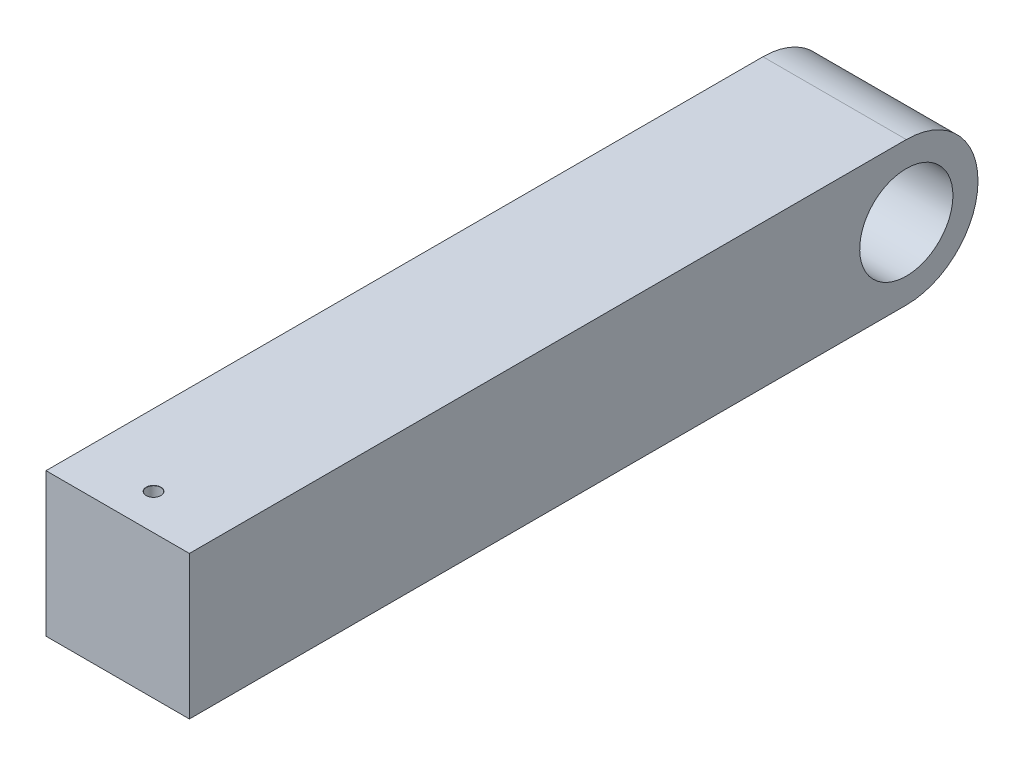
SolidWorks part; units mm, degrees
ref_plane "Front Plane" through (0, 0, 0) normal (1, 0, 0) x (0, 1, 0)
ref_plane "Top Plane" through (0, 0, 0) normal (0, 0, 1) x (0, 1, 0)
ref_plane "Right Plane" through (0, 0, 0) normal (0, 1, 0) x (-1, 0, 0)
sketch "Sketch1" plane through (0, 0, 0) normal (0, 0, 1) x (0, 1, 0)
  line L1 (-10, 10) -> (10, 10)
  line L2 (-10, 10) -> (-10, -10)
  line L3 (-10, -10) -> (10, -10)
  line L4 (10, 10) -> (10, -10)
  point P4 (-10, 0)
  point P6 (0, 10)
  dimension "D1" = 20
  dimension "D2" = 20
  dimension "D3" = 0
  dimension "D4" = 0
extrude "Boss-Extrude1" add sketch "Sketch1" against normal blind 110
fillet "Fillet1" radius 10 2 edges at (0, -10, -110) (0, 10, -110)
sketch "Sketch2" plane through (10, 0, 0) normal (1, 0, 0) x (0, 1, 0)
  line L3 (-10, 0) -> (-10, -100)
  line L4 (10, -100) -> (10, 0)
  line L5 (10, 0) -> (-10, 0)
  line L6 (-10, 0) -> (-10, -100)
  line L7 (10, -100) -> (10, 0)
  line L8 (10, 0) -> (-10, 0)
  circle A0 centre (0, -100) radius 6.5
  arc A2 (-10, -100) -> (0, -110) centre (0, -100) ccw
  arc A3 (0, -110) -> (10, -100) centre (0, -100) ccw
  arc A4 (-10, -100) -> (0, -110) centre (0, -100) ccw
  arc A5 (0, -110) -> (10, -100) centre (0, -100) ccw
  dimension "D2" = 13
  dimension "D1" = 0
extrude "Cut-Extrude1" cut sketch "Sketch2" against normal up to surface (20 mm away) contours A0 region at (10, 0, -100) up to face at (-10, 0, -62.8284)
hole_wizard "Ø2.0mm Dowel Hole1" positions "Sketch4" profile "Sketch5" hole size "Ø2.0" standard "IS" end condition through all
sketch "Sketch4" plane through (0, -10, 0) normal (0, -1, 0) x (1, 0, 0)
  point P0 (0, -5)
  dimension "D1" = 5
sketch "Sketch5" plane through (0, -10, -5) normal (1, 0, 0) x (0, 0, -1)
  line L0 (0, 0) -> (0, 20)
  line L1 (0, 20) -> (1, 20)
  line L2 (1, 20) -> (1, 0.025)
  line L3 (1, 0.025) -> (1.025, 0)
  line L5 (1.025, 0) -> (0, 0)
  line L6 (-1, 0.025) -> (-1.025, 0) construction
  line L11 (0, -6.35) -> (0, 107.95) construction
  dimension "Thru Hole Dia." = 2
  dimension "Thru Hole Depth" = 20
  dimension "Near C'Sink Dia." = 2.05
  dimension "Near C'Sink Angle" = 90
mirror "Mirror1" about plane through (0, 0, 0) normal (0, 1, 0) of "Ø2.0mm Dowel Hole1"
